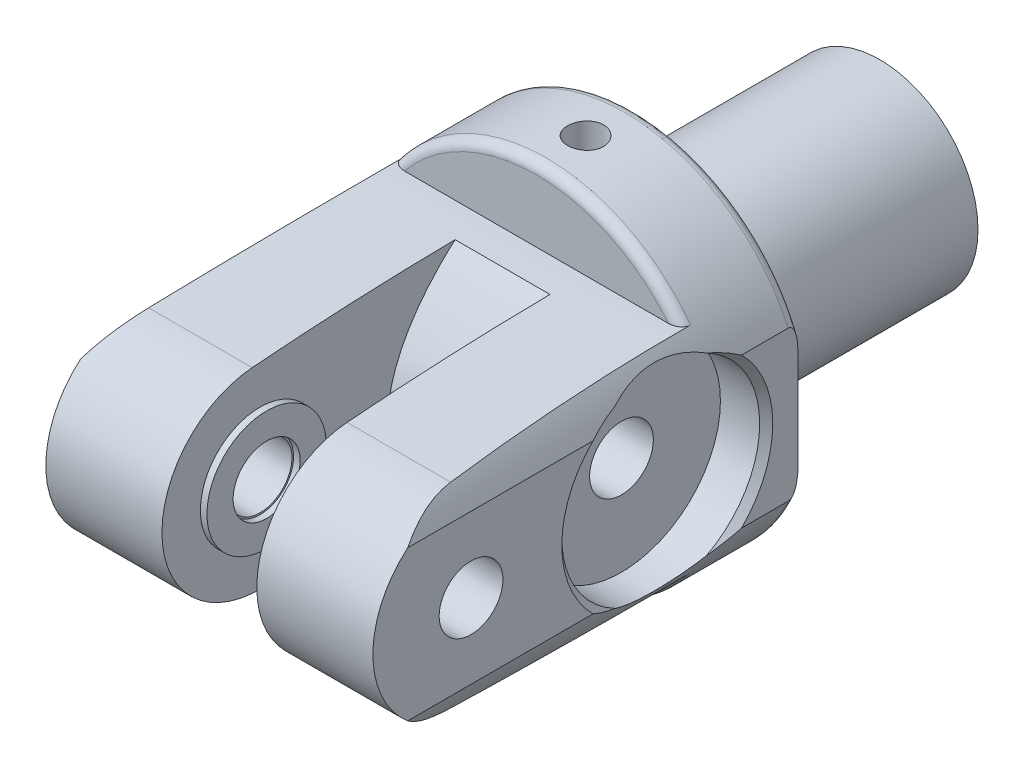
SolidWorks part; units mm, degrees
ref_plane "前视基准面" through (0, 0, 0) normal (0, 0, 1) x (1, 0, 0)
ref_plane "上视基准面" through (0, 0, 0) normal (0, 1, 0) x (1, 0, 0)
ref_plane "右视基准面" through (0, 0, 0) normal (1, 0, 0) x (0, 0, -1)
sketch "草图1" plane through (0, 0, 0) normal (0, 0, 1) x (1, 0, 0)
  line L0 (0, 0) -> (0, 5.5) construction
  line L1 (-5, 2.2913) -> (-5, -2.2913)
  line L2 (5, 2.2913) -> (5, -2.2913)
  arc A0 (-5, -2.2913) -> (5, -2.2913) centre (0, 0) ccw
  arc A1 (5, 2.2913) -> (-5, 2.2913) centre (0, 0) ccw
  dimension "D1" = 11
  dimension "D2" = 10
extrude "凸台-拉伸1" add sketch "草图1" along normal blind 3
sketch "草图4" plane through (0, 0, 0) normal (1, 0, 0) x (0, 0, -1)
  line L0 (0, 0) -> (-10, 0) construction
  line L1 (-3, -2.2913) -> (-3, -5.5) construction
  line L2 (0, -2.2913) -> (0, 2.2913) construction
  line L3 (-3, 3.2821) -> (-3, -3.2821)
  arc A0 (-10.2414, 2.9903) -> (-10.2414, -2.9903) centre (-10, 0) ccw
  arc A2 (-3, 3.2821) -> (-10.2414, 2.9903) centre (-3, -86.7179) ccw
  arc A3 (-3, -3.2821) -> (-10.2414, -2.9903) centre (-3, 86.7179) cw
  dimension "D1" = 90
  dimension "D2" = 6
  dimension "D3" = 10
extrude "凸台-拉伸3" add sketch "草图4" along normal blind 5 and the other way blind 5
sketch "草图5" plane through (0, 0, 0) normal (0, 0, -1) x (-1, 0, 0)
  circle A0 centre (0, 0) radius 5.5
  circle A1 centre (0, 0) radius 6.3654
extrude "切除-拉伸1" cut sketch "草图5" against normal blind 14
sketch "草图6" plane through (0, 0, 0) normal (1, 0, 0) x (0, 0, -1)
  line L0 (-10, 0) -> (-4, 0) construction
  circle A0 centre (-10, 0) radius 0.975
  circle A1 centre (-4, 0) radius 0.975
  dimension "D2" = 1.95
  dimension "D3" = 1.95
  dimension "D1" = 6
extrude "切除-拉伸2" cut sketch "草图6" against normal through all both and the other way through all
sketch "草图7" plane through (0, 0, 0) normal (0, 0, -1) x (-1, 0, 0)
  circle A0 centre (0, 0) radius 3
  circle A1 centre (0, 0) radius 0.9
  dimension "D1" = 6
  dimension "D2" = 1.8
extrude "凸台-拉伸4" add sketch "草图7" along normal blind 7.5
sketch "草图8" plane through (0, 0, 0) normal (1, 0, 0) x (0, 0, -1)
  line L0 (-10, 0) -> (-4, 0) construction
  arc A1 (-3, 3.2821) -> (-10.2414, 2.9903) centre (-3, -86.7179) ccw construction
  arc A2 (-4.0378, 3.2761) -> (-10.2414, 2.9903) centre (-3, -86.7179) ccw
  arc A3 (-10.2414, -2.9903) -> (-3, -3.2821) centre (-3, 86.7179) ccw construction
  arc A4 (-11.9365, -2.2913) -> (-10.2414, -2.9903) centre (-10, 0) ccw construction
  arc A5 (-11.9365, 2.2913) -> (-11.9365, -2.2913) centre (-10, 0) ccw construction
  arc A6 (-10.2414, 2.9903) -> (-11.9365, 2.2913) centre (-10, 0) ccw construction
  arc A7 (-10.2414, -2.9903) -> (-4.0378, -3.2761) centre (-3, 86.7179) ccw
  arc A8 (-11.9365, -2.2913) -> (-10.2414, -2.9903) centre (-10, 0) ccw
  arc A9 (-11.9365, 2.2913) -> (-11.9365, -2.2913) centre (-10, 0) ccw
  arc A10 (-10.2414, 2.9903) -> (-11.9365, 2.2913) centre (-10, 0) ccw
  spline S2 degree 3 poles (-6.0666, 0) (-5.8466, 1.3089) (-5.0096, 2.4176) (-4.0378, 3.2761) knots 0 0 0 0 1 1 1 1
  spline S3 degree 3 poles (-6.0666, 0) (-5.8466, -1.3089) (-5.0096, -2.4176) (-4.0378, -3.2761) knots 0 0 0 0 1 1 1 1
extrude "切除-拉伸3" cut sketch "草图8" against normal blind 1.45 and the other way blind 1.45
sketch "草图10" plane through (1.45, 0, 0) normal (-1, 0, 0) x (0, 0, 1)
  circle A0 centre (10, 0) radius 1.025
  circle A1 centre (10, 0) radius 1.825
  dimension "D1" = 0.8
extrude "凸台-拉伸5" add sketch "草图10" along normal blind 0.2
sketch "草图11" plane through (5, 0, 0) normal (1, 0, 0) x (0, 0, -1)
  circle A0 centre (-4, 0) radius 3.025
  dimension "D1" = 6.05
extrude "切除-拉伸4" cut sketch "草图11" against normal blind 1.4
mirror "镜向1" about plane through (0, 0, 0) normal (1, 0, 0) of "切除-拉伸4", "凸台-拉伸5"
sketch "草图12" plane through (0, 0, 0) normal (0, 0, -1) x (-1, 0, 0)
  circle A0 centre (0, 0) radius 4.2
  circle A1 centre (0, 0) radius 3 construction
  dimension "D1" = 1.2
extrude "凸台-拉伸6" add sketch "草图12" along normal blind 0.4
fillet "圆角3" radius 0.3 4 edges at (0, -5.5, 3) (0, -5.5, 0) (0, 5.5, 3) (0, 5.5, 0)
chamfer "倒角1" distance 0.2 angle 45 4 edges at (-5, 0, 7.025) (-5, 0, 0.975) (5, 0, 0.975) (5, 0, 7.025)
ref_plane "基准面1" through (0, -6, 0) normal (0, 1, 0) x (1, 0, 0)
sketch "草图14" plane through (0, -6, 0) normal (0, 1, 0) x (1, 0, 0)
  line L0 (0, 7.5) -> (0, -4.0378) construction
  line L1 (3, 7.5) -> (-3, 7.5) construction
  line L2 (1.45, -4.0378) -> (-1.45, -4.0378) construction
  line L3 (5, 0) -> (-5, 0) construction
  circle A0 centre (0, -1.5) radius 1
  dimension "D1" = 1.5
  dimension "D2" = 2
extrude "切除-拉伸5" cut sketch "草图14" along normal blind 5
sketch "草图15" plane through (0, -1, 0) normal (0, -1, 0) x (1, 0, 0)
  circle A0 centre (0, 1.5) radius 0.55
  dimension "D1" = 1.1
extrude "切除-拉伸6" cut sketch "草图15" against normal blind 7
